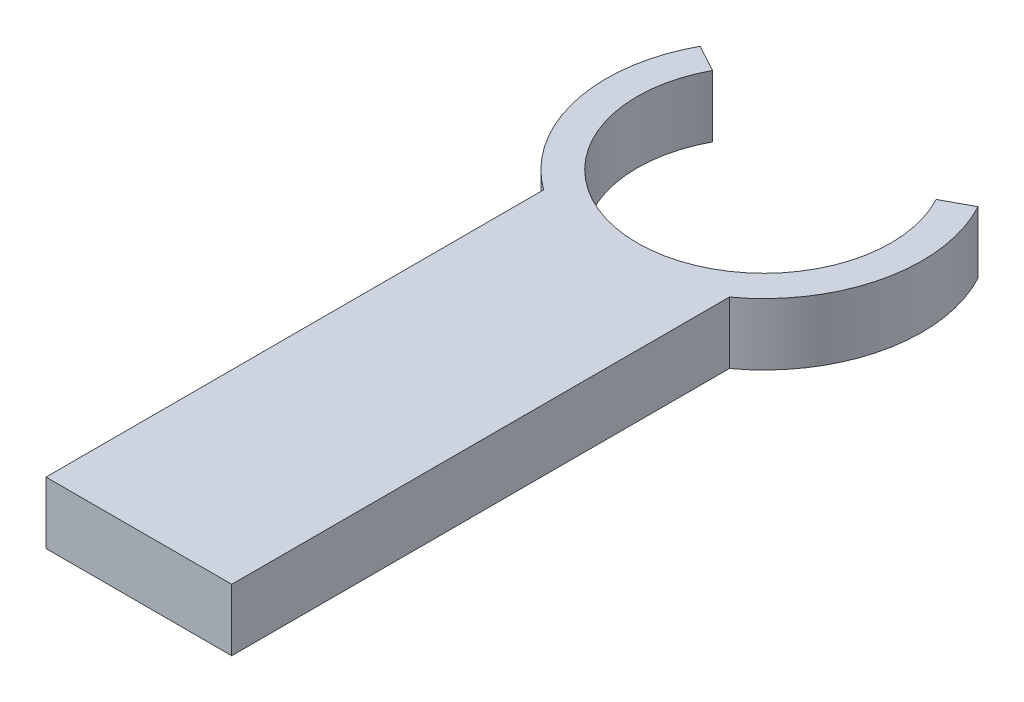
SolidWorks part; units mm, degrees
ref_plane "Front Plane" through (0, 0, 0) normal (0, 0, 1) x (1, 0, 0)
ref_plane "Top Plane" through (0, 0, 0) normal (0, 1, 0) x (1, 0, 0)
ref_plane "Right Plane" through (0, 0, 0) normal (1, 0, 0) x (0, 0, -1)
sketch "Sketch1" plane through (0, 0, 0) normal (0, 1, 0) x (1, 0, 0)
  line L3 (0, -20.5) -> (0, -25.5) construction
  line L4 (-15, -101) -> (15, -101) construction
  line L5 (-15, -101) -> (15, -101)
  line L6 (-15, -101) -> (-14.9913, -20.6279)
  line L7 (15, -101) -> (15.0087, -20.6153)
  line L9 (-18.0472, 9.7237) -> (-22.4489, 12.0953)
  line L10 (18.0472, 9.7237) -> (22.4489, 12.0953)
  arc A0 (-18.0472, 9.7237) -> (18.0472, 9.7237) centre (0, 0) ccw
  arc A1 (-22.4489, 12.0953) -> (-14.9913, -20.6279) centre (0, 0) ccw
  arc A2 (15.0087, -20.6153) -> (22.4489, 12.0953) centre (0, 0) ccw
  point P12 (0, -101)
  dimension "D1" = 41
  dimension "D2" = 51
  dimension "D4" = 30
extrude "Boss-Extrude1" add sketch "Sketch1" along normal blind 10
